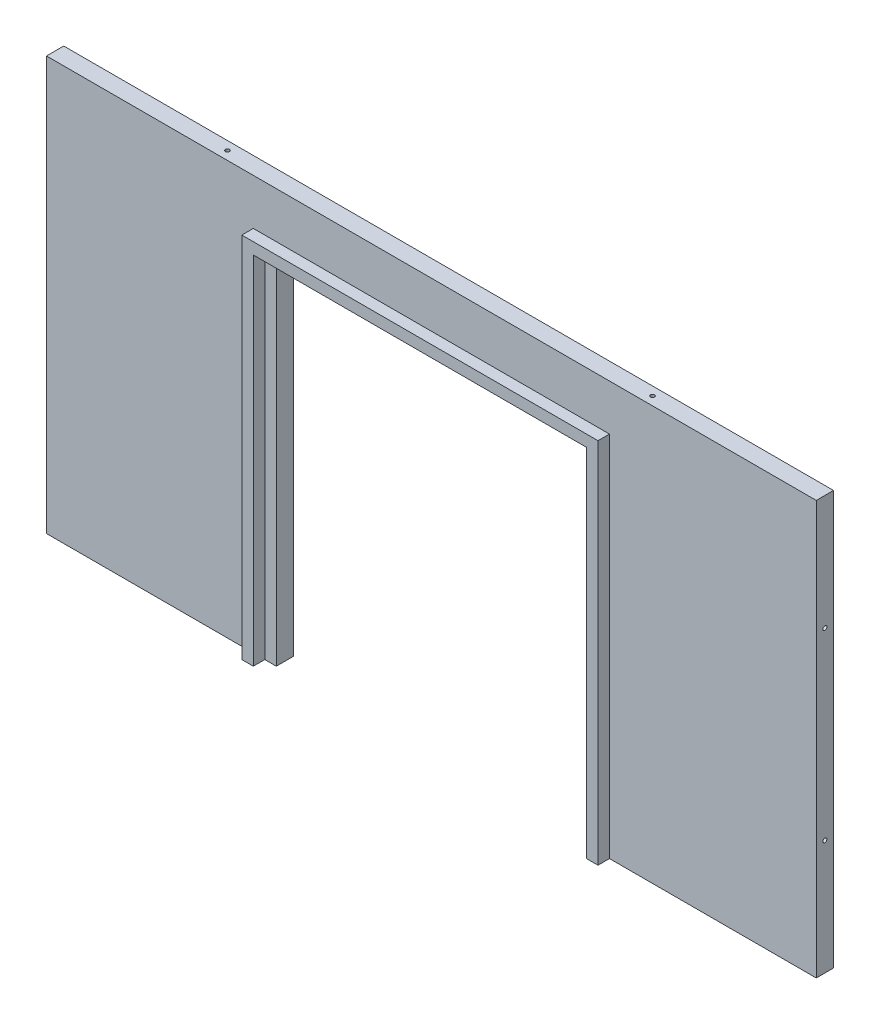
SolidWorks part; units mm, degrees
ref_plane "前视基准面" through (0, 0, 0) normal (0, 0, 1) x (1, 0, 0)
ref_plane "上视基准面" through (0, 0, 0) normal (0, 1, 0) x (1, 0, 0)
ref_plane "右视基准面" through (0, 0, 0) normal (1, 0, 0) x (0, 0, -1)
other "Configuration Table"
sketch "草图1" plane through (0, 0, 0) normal (0, 0, 1) x (1, 0, 0)
  line L61 (-67, 36) -> (67, 36)
  line L62 (-67, 36) -> (-67, -36)
  line L63 (-67, -36) -> (67, -36)
  line L64 (67, 36) -> (67, -36)
  point P4 (0, 36)
  point P5 (-67, 0)
  dimension "D1" = 72
  dimension "D2" = 134
extrude "凸台-拉伸1" add sketch "草图1" along normal blind 3
sketch "草图2" plane through (0, 0, 3) normal (0, 0, 1) x (1, 0, 0)
  line L0 (-67, -36) -> (67, -36) construction
  line L1 (-29, 26) -> (29, 26)
  line L2 (-29, 26) -> (-29, -36)
  line L3 (-29, -36) -> (29, -36)
  line L4 (29, 26) -> (29, -36)
  line L6 (-31, 28) -> (-29, 28)
  line L7 (-31, 28) -> (-31, -36)
  line L8 (-31, -36) -> (-29, -36)
  line L9 (-29, 28) -> (-29, -36)
  line L10 (29, -36) -> (31, -36)
  line L11 (29, -36) -> (29, 28)
  line L12 (29, 28) -> (31, 28)
  line L13 (31, -36) -> (31, 28)
  line L14 (-29, 28) -> (29, 28)
  line L15 (-29, 28) -> (-29, 26)
  line L16 (-29, 26) -> (29, 26)
  line L17 (29, 28) -> (29, 26)
  line L18 (-27, 24) -> (27, 24)
  line L19 (-27, 24) -> (-27, -36)
  line L20 (-27, -36) -> (27, -36)
  line L21 (27, 24) -> (27, -36)
  point P6 (0, 26)
  point P18 (0, 24)
  line M4 (-67, -36) -> (67, -36)
  dimension "D1" = 62
  dimension "D2" = 58
  dimension "D3" = 2
  dimension "D4" = 2
  dimension "D5" = 2
  dimension "D6" = 2
extrude "切除-拉伸1" cut sketch "草图2" against normal through all contours L4 L3 L2 L1
extrude "凸台-拉伸2" add sketch "草图2<4>" along normal blind 2 contours L9 L6 L7 L2 M4 | L14 L9 L1 L11 | L13 L12 L11 L4 M4 region at (0, 27, 3) region at (-30, -4, 3) region at (30, -4, 3)
sketch "草图2<4>" plane through (0, 0, 3) normal (0, 0, 1) x (1, 0, 0) same geometry as "草图2"
extrude "凸台-拉伸3" add sketch "草图2<5>" against normal blind 3 contours L18 L21 L4 L1 L2 L19 M4 region at (0, 25.151, 3)
sketch "草图2<5>" plane through (0, 0, 3) normal (0, 0, 1) x (1, 0, 0) same geometry as "草图2"
sketch "草图3" plane through (0, 24, 0) normal (0, -1, 0) x (1, 0, 0)
  line L0 (27, 0) -> (27, 3) construction
  line L1 (-27, 3) -> (27, 3)
  line L2 (-27, 3) -> (-27, 1.5)
  line L3 (-27, 1.5) -> (27, 1.5)
  line L4 (27, 3) -> (27, 1.5)
extrude "切除-拉伸2" cut sketch "草图3" against normal blind 3 contours L3 L4 L1 L2
sketch "草图4" plane through (0, -36, 0) normal (0, -1, 0) x (1, 0, 0)
  line L2 (-37, 1.5) -> (-67, 1.5)
  line L6 (37, 1.5) -> (67, 1.5)
  line L7 (67, 3) -> (67, 0) construction
  line L8 (-67, 3) -> (-67, 0) construction
  circle A0 centre (-37, 1.5) radius 0.35
  circle A1 centre (37, 1.5) radius 0.35
  point P4 (0, 0)
  dimension "D2" = 0.7
  dimension "D1" = 30
extrude "切除-拉伸3" cut sketch "草图4" against normal blind 1.5 contours A0 | A1
extrude "切除-拉伸4" cut sketch "草图4<3>" along normal blind 1.5 from surface contours A0 | A1 starting at face at (0, 36, 1.5)
sketch "草图4<3>" plane through (0, -36, 0) normal (0, -1, 0) x (1, 0, 0) same geometry as "草图4"
sketch "草图5" plane through (67, 0, 0) normal (1, 0, 0) x (0, 0, -1)
  line L0 (-1.5, 16) -> (-1.5, -16)
  line L1 (-3, 36) -> (0, 36) construction
  circle A0 centre (-1.5, 16) radius 0.35
  circle A1 centre (-1.5, -16) radius 0.35
  point P4 (-1.5, 0)
  point P8 (-1.5, 36)
  dimension "D1" = 0.7
  dimension "D2" = 20
extrude "切除-拉伸5" cut sketch "草图5" against normal blind 1.5 contours A1 | A0
extrude "切除-拉伸6" cut sketch "草图5<3>" along normal blind 1.5 from surface contours A0 | A1 starting at face at (-67, 0, 1.5)
sketch "草图5<3>" plane through (67, 0, 0) normal (1, 0, 0) x (0, 0, -1) same geometry as "草图5"
